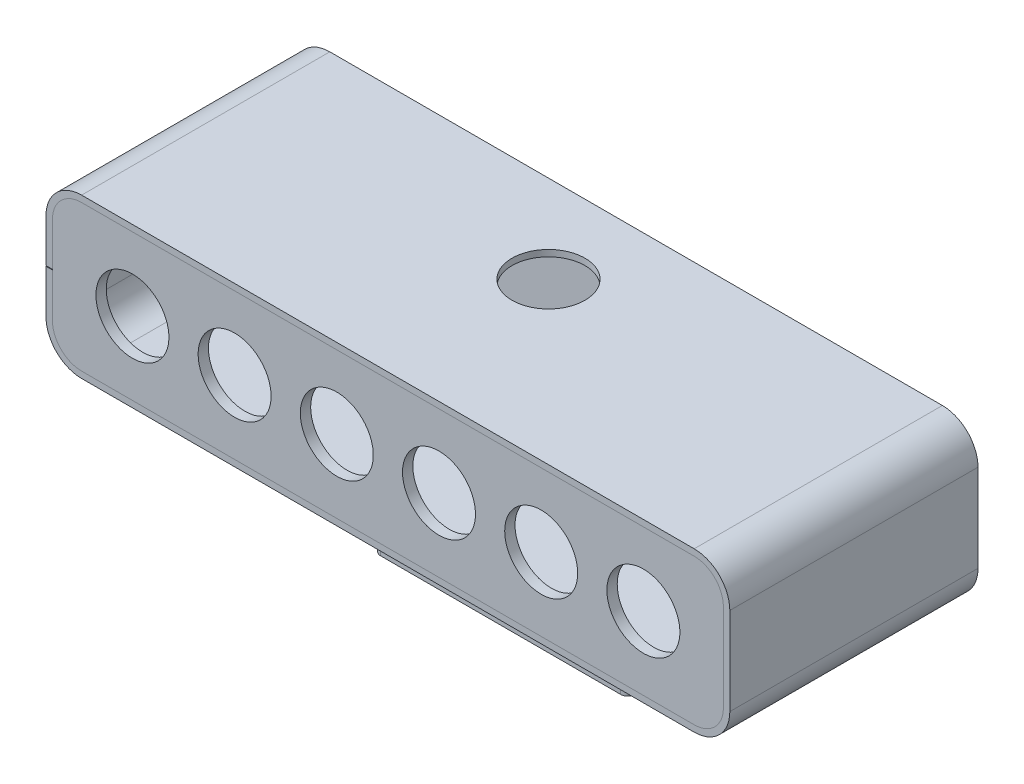
SolidWorks part; units mm, degrees
material "Acrylic (Medium-high impact)"
ref_plane "Front" through (0, 0, 0) normal (0, 0, 1) x (1, 0, 0)
ref_plane "Top" through (0, 0, 0) normal (0, 1, 0) x (1, 0, 0)
ref_plane "Right" through (0, 0, 0) normal (1, 0, 0) x (0, 0, -1)
sketch "Sketch5" plane through (0, 0, 0) normal (0, 1, 0) x (1, 0, 0)
  line L1 (0, 0) -> (-692.15, 0)
  line L2 (0, 0) -> (0, 107.95)
  line L3 (0, 107.95) -> (-692.15, 107.95)
  line L4 (-692.15, 0) -> (-692.15, 107.95)
  dimension "D1" = 107.95
  dimension "D2" = 692.15
extrude "Boss-Extrude4" [suppressed] add sketch "Sketch5" along normal blind 2.794
sketch "Sketch1" plane through (0, 0, 0) normal (0, 0, 1) x (1, 0, 0)
  line L1 (-145.923, 31.75) -> (145.923, 31.75)
  line L2 (-145.923, 31.75) -> (-145.923, -31.75)
  line L3 (-145.923, -31.75) -> (145.923, -31.75)
  line L4 (145.923, 31.75) -> (145.923, -31.75)
  line L5 (-145.923, 31.75) -> (145.923, -31.75) construction
  line L6 (-145.923, -31.75) -> (145.923, 31.75) construction
  point P0 (0, 0)
  dimension "D1" = 291.846
  dimension "D2" = 63.5
extrude "Boss-Extrude1" add sketch "Sketch1" along normal blind 4.4958
fillet "Fillet1" radius 12.7 4 edges at (-145.923, -31.75, 2.2479) (145.923, -31.75, 2.2479) (145.923, 31.75, 2.2479) (-145.923, 31.75, 2.2479)
sketch "Sketch3" plane through (0, 0, 0) normal (0, 0, 1) x (1, 0, 0)
  line L0 (133.223, 34.544) -> (-133.223, 34.544)
  line L1 (-148.717, 19.05) -> (-148.717, 0.254)
  line L2 (-133.223, -34.544) -> (133.223, -34.544)
  line L3 (148.717, -19.05) -> (148.717, 19.05)
  line L4 (-133.223, -31.75) -> (133.223, -31.75)
  line L5 (-145.923, 19.05) -> (-145.923, -19.05)
  line L6 (133.223, 31.75) -> (-133.223, 31.75)
  line L7 (145.923, -19.05) -> (145.923, 19.05)
  line L8 (-133.223, -31.75) -> (133.223, -31.75)
  line L9 (-145.923, 19.05) -> (-145.923, 0.254)
  line L10 (133.223, 31.75) -> (-133.223, 31.75)
  line L11 (145.923, -19.05) -> (145.923, 19.05)
  line L12 (-145.923, 0) -> (-148.717, 0)
  line L13 (-145.923, 0.254) -> (-148.717, 0.254)
  line L14 (-145.923, 0) -> (-145.923, -19.05)
  line L15 (-145.923, 19.05) -> (-145.923, -19.05) construction
  line L16 (-148.717, 0) -> (-148.717, -19.05)
  line L17 (-148.717, 19.05) -> (-148.717, -19.05) construction
  line L18 (-145.923, 19.05) -> (-145.923, -19.05) construction
  arc A0 (-133.223, 34.544) -> (-148.717, 19.05) centre (-133.223, 19.05) ccw
  arc A1 (-148.717, -19.05) -> (-133.223, -34.544) centre (-133.223, -19.05) ccw
  arc A2 (133.223, -34.544) -> (148.717, -19.05) centre (133.223, -19.05) ccw
  arc A3 (148.717, 19.05) -> (133.223, 34.544) centre (133.223, 19.05) ccw
  arc A4 (-145.923, -19.05) -> (-133.223, -31.75) centre (-133.223, -19.05) ccw
  arc A5 (-133.223, 31.75) -> (-145.923, 19.05) centre (-133.223, 19.05) ccw
  arc A6 (145.923, 19.05) -> (133.223, 31.75) centre (133.223, 19.05) ccw
  arc A7 (133.223, -31.75) -> (145.923, -19.05) centre (133.223, -19.05) ccw
  arc A8 (-145.923, -19.05) -> (-133.223, -31.75) centre (-133.223, -19.05) ccw
  arc A9 (-133.223, 31.75) -> (-145.923, 19.05) centre (-133.223, 19.05) ccw
  arc A10 (145.923, 19.05) -> (133.223, 31.75) centre (133.223, 19.05) ccw
  arc A11 (133.223, -31.75) -> (145.923, -19.05) centre (133.223, -19.05) ccw
  dimension "D3" = 0.254
  dimension "D1" = 0
  dimension "D2" = 2.794
extrude "Boss-Extrude2" add sketch "Sketch3" along normal blind 107.95 separate body
sketch "Sketch4" plane through (0, 0, 107.95) normal (0, 0, 1) x (1, 0, 0)
  line L4 (-145.923, 19.05) -> (-145.923, -19.05)
  line L5 (-133.223, -31.75) -> (133.223, -31.75)
  line L6 (145.923, -19.05) -> (145.923, 19.05)
  line L7 (133.223, 31.75) -> (-133.223, 31.75)
  line L8 (-145.923, 19.05) -> (-145.923, -19.05)
  line L9 (-133.223, -31.75) -> (133.223, -31.75)
  line L10 (145.923, -19.05) -> (145.923, 19.05)
  line L11 (133.223, 31.75) -> (-133.223, 31.75)
  arc A4 (-145.923, -19.05) -> (-133.223, -31.75) centre (-133.223, -19.05) ccw
  arc A5 (133.223, -31.75) -> (145.923, -19.05) centre (133.223, -19.05) ccw
  arc A6 (145.923, 19.05) -> (133.223, 31.75) centre (133.223, 19.05) ccw
  arc A7 (-133.223, 31.75) -> (-145.923, 19.05) centre (-133.223, 19.05) ccw
  arc A8 (-145.923, -19.05) -> (-133.223, -31.75) centre (-133.223, -19.05) ccw
  arc A9 (133.223, -31.75) -> (145.923, -19.05) centre (133.223, -19.05) ccw
  arc A10 (145.923, 19.05) -> (133.223, 31.75) centre (133.223, 19.05) ccw
  arc A11 (-133.223, 31.75) -> (-145.923, 19.05) centre (-133.223, 19.05) ccw
  dimension "D1" = 0
extrude "Boss-Extrude3" add sketch "Sketch4" against normal blind 4.4958 separate body
sketch "Sketch2" plane through (0, 0, 0) normal (0, 0, -1) x (-1, 0, 0)
  line L0 (22.225, 0) -> (-22.225, 0) construction
  line L1 (22.225, 0) -> (66.675, 0) construction
  line L2 (66.675, 0) -> (111.125, 0) construction
  line L3 (-22.225, 0) -> (-66.675, 0) construction
  line L4 (-66.675, 0) -> (-111.125, 0) construction
  line L5 (-111.125, 0) -> (-127, 0) construction
  line L6 (111.125, 0) -> (127, 0) construction
  circle A0 centre (-111.125, 0) radius 15.875
  circle A1 centre (-66.675, 0) radius 15.875
  circle A2 centre (-22.225, 0) radius 15.875
  circle A3 centre (22.225, 0) radius 15.875
  circle A4 centre (66.675, 0) radius 15.875
  circle A5 centre (111.125, 0) radius 15.875
  dimension "D1" = 31.75
  dimension "D2" = 254
extrude "Cut-Extrude1" cut sketch "Sketch2" against normal through all
sketch "Sketch6" plane through (0, -34.544, 0) normal (0, -1, 0) x (1, 0, 0)
  line L0 (0, 0) -> (0, 31.369) construction
  line L1 (-133.223, 0) -> (133.223, 0) construction
  line L2 (-52.705, 55.928) -> (-52.705, 6.81)
  line L3 (-52.245, 58.928) -> (52.245, 58.928)
  line L4 (-55.245, 55.928) -> (-55.245, 6.81)
  line L5 (-52.245, 3.81) -> (52.245, 3.81)
  line L6 (55.245, 55.928) -> (55.245, 6.81)
  line L7 (-55.245, 58.928) -> (55.245, 3.81) construction
  line L8 (-55.245, 3.81) -> (55.245, 58.928) construction
  line L9 (-52.245, 6.35) -> (52.245, 6.35)
  line L10 (52.705, 55.928) -> (52.705, 6.81)
  line L11 (-52.245, 56.388) -> (52.245, 56.388)
  arc A0 (-55.245, 6.81) -> (-52.245, 3.81) centre (-52.245, 6.81) ccw
  arc A1 (55.245, 6.81) -> (52.245, 3.81) centre (52.245, 6.81) cw
  arc A2 (55.245, 55.928) -> (52.245, 58.928) centre (52.245, 55.928) ccw
  arc A3 (-52.245, 58.928) -> (-55.245, 55.928) centre (-52.245, 55.928) ccw
  arc A4 (-52.705, 6.81) -> (-52.245, 6.35) centre (-52.245, 6.81) ccw
  arc A5 (52.705, 6.81) -> (52.245, 6.35) centre (52.245, 6.81) cw
  arc A6 (52.705, 55.928) -> (52.245, 56.388) centre (52.245, 55.928) ccw
  arc A7 (-52.245, 56.388) -> (-52.705, 55.928) centre (-52.245, 55.928) ccw
  dimension "D4" = 3
  dimension "D1" = 110.49
  dimension "D2" = 55.118
  dimension "D3" = 3.81
  dimension "D5" = 2.54
extrude "Boss-Extrude5" add sketch "Sketch6" along normal blind 50.8 separate body
sketch "Sketch7" plane through (0, 0, 0) normal (0, 0, -1) x (-1, 0, 0)
  line L0 (0, 0) -> (-52.3875, 0) construction
  line L1 (0, 0) -> (52.3875, 0) construction
  circle A0 centre (-52.3875, 0) radius 3.175
  circle A1 centre (52.3875, 0) radius 3.175
  dimension "D1" = 6.35
  dimension "D2" = 104.775
extrude "Cut-Extrude2" cut sketch "Sketch7" against normal up to next (4.4958 mm away)
sketch "Sketch8" plane through (0, -34.544, 0) normal (0, -1, 0) x (1, 0, 0)
  line L0 (0, 3.81) -> (0, 58.928) construction
  line L1 (-52.245, 3.81) -> (52.245, 3.81) construction
  line L2 (52.245, 58.928) -> (-52.245, 58.928) construction
  line L4 (-46.355, 53.594) -> (46.355, 53.594)
  line L5 (-50.165, 49.784) -> (-50.165, 12.954)
  line L6 (-46.355, 9.144) -> (46.355, 9.144)
  line L7 (50.165, 49.784) -> (50.165, 12.954)
  line L8 (-50.165, 53.594) -> (50.165, 9.144) construction
  line L9 (-50.165, 9.144) -> (50.165, 53.594) construction
  arc A0 (-50.165, 12.954) -> (-46.355, 9.144) centre (-46.355, 12.954) ccw
  arc A1 (50.165, 12.954) -> (46.355, 9.144) centre (46.355, 12.954) cw
  arc A2 (50.165, 49.784) -> (46.355, 53.594) centre (46.355, 49.784) ccw
  arc A3 (-46.355, 53.594) -> (-50.165, 49.784) centre (-46.355, 49.784) ccw
  point P6 (0, 31.369)
  dimension "D3" = 3.81
  dimension "D1" = 100.33
  dimension "D2" = 44.45
extrude "Cut-Extrude3" cut sketch "Sketch8" against normal up to next (2.794 mm away)
sketch "Sketch9" plane through (0, -34.544, 0) normal (0, -1, 0) x (1, 0, 0)
  line L2 (0, 0) -> (0, 38.1) construction
  circle A0 centre (0, 38.1) radius 15.875
  dimension "D1" = 31.75
  dimension "D2" = 38.1
extrude "Cut-Extrude4" cut sketch "Sketch9" against normal through all from surface starting at face at (0, 31.75, 53.975)
sketch "Sketch10" plane through (0, -34.544, 0) normal (0, -1, 0) x (1, 0, 0)
  circle A0 centre (63.5, 50.8) radius 1.7463
  circle A1 centre (63.5, 12.7) radius 1.7463
  circle A2 centre (-63.5, 50.8) radius 1.7462
  circle A3 centre (-63.5, 12.7) radius 1.7462
  arc A5 (-61.7042, 48.1817) -> (-60.3345, 51.046) centre (-63.5, 50.8) ccw construction
  arc A6 (-63.8073, 9.5399) -> (-60.9169, 10.8538) centre (-63.5, 12.7) ccw construction
  circle A7 centre (63.5, 50.8) radius 1.4732 construction
  circle A8 centre (63.5, 12.7) radius 1.4732 construction
  dimension "D1" = 3.4925
extrude "Cut-Extrude5" cut sketch "Sketch10" against normal up to next (2.794 mm away)
sketch "Sketch11" [suppressed] plane through (0, -31.75, 0) normal (0, 1, 0) x (1, 0, 0)
  line L0 (-133.223, -107.95) -> (-133.223, 0) construction
  line L1 (-133.223, -107.95) -> (-133.223, 0)
  line L2 (133.223, -107.95) -> (133.223, 0) construction
  line L3 (133.223, -107.95) -> (133.223, 0)
  line L4 (133.223, -107.95) -> (148.717, -107.95)
  line L5 (148.717, -107.95) -> (148.717, 0)
  line L6 (148.717, 0) -> (133.223, 0)
  line L7 (-133.223, 0) -> (-148.717, 0)
  line L8 (-148.717, 0) -> (-148.717, -107.95)
  line L9 (-148.717, -107.95) -> (-133.223, -107.95)
extrude "Cut-Extrude6" [suppressed] cut sketch "Sketch11" along normal through all
sketch "Sketch12" [suppressed] plane through (0, -31.75, 0) normal (0, 1, 0) x (1, 0, 0)
  line L0 (-133.223, -107.95) -> (-133.223, 0) construction
  line L1 (-133.223, -107.95) -> (-133.223, 0)
  line L2 (133.223, -107.95) -> (133.223, 0) construction
  line L3 (133.223, -107.95) -> (133.223, 0)
  line L4 (-142.0985, 0) -> (-142.0985, -107.95) construction
  line L5 (142.0985, 0) -> (-142.0985, 0) construction
  line L6 (142.0985, -107.95) -> (142.0985, 0) construction
  line L7 (142.0985, -107.95) -> (-142.0985, -107.95) construction
  line L8 (-142.0985, 0) -> (-142.0985, -107.95)
  line L9 (142.0985, 0) -> (133.223, 0)
  line L10 (142.0985, -107.95) -> (142.0985, 0)
  line L11 (142.0985, -107.95) -> (133.223, -107.95)
  line L12 (-133.223, -107.95) -> (-142.0985, -107.95)
  line L13 (-133.223, 0) -> (-142.0985, 0)
extrude "Cut-Extrude7" [suppressed] cut sketch "Sketch12" against normal through all
sketch "Sketch13" [suppressed] plane through (0, 34.544, 0) normal (0, 1, 0) x (1, 0, 0)
  line L4 (133.223, 0) -> (-133.223, 0)
  line L5 (-133.223, 0) -> (-133.223, -107.95)
  line L6 (-133.223, -107.95) -> (133.223, -107.95)
  line L7 (133.223, -107.95) -> (133.223, 0)
  line L8 (133.223, 0) -> (-133.223, 0)
  line L9 (-133.223, 0) -> (-133.223, -107.95)
  line L10 (-133.223, -107.95) -> (133.223, -107.95)
  line L11 (133.223, -107.95) -> (133.223, 0)
  dimension "D1" = 0
extrude "Cut-Extrude8" [suppressed] cut sketch "Sketch13" against normal up to surface (2.794 mm away) up to face at (-15.875, 31.75, 38.1)
sketch "Sketch14" [suppressed] plane through (0, -31.75, 0) normal (0, 1, 0) x (1, 0, 0)
  line L1 (-133.223, -107.95) -> (-171.323, -107.95)
  line L2 (-133.223, -107.95) -> (-133.223, 0)
  line L3 (-133.223, 0) -> (-171.323, 0)
  line L4 (-171.323, -107.95) -> (-171.323, 0)
  dimension "D1" = 38.1
sketch "Sketch15" [suppressed] plane through (0, -31.75, 0) normal (0, 1, 0) x (1, 0, 0)
  line L0 (-133.223, -107.95) -> (-133.223, 0) construction
  line L1 (133.223, -107.95) -> (558.927, -107.95)
  line L2 (133.223, -107.95) -> (133.223, 0)
  line L3 (133.223, 0) -> (558.927, 0)
  line L4 (558.927, -107.95) -> (558.927, 0)
  dimension "D1" = 692.15
extrude "Boss-Extrude6" [suppressed] add sketch "Sketch15" against normal up to surface (2.794 mm away) up to face at (65.2463, -34.544, 12.7)
